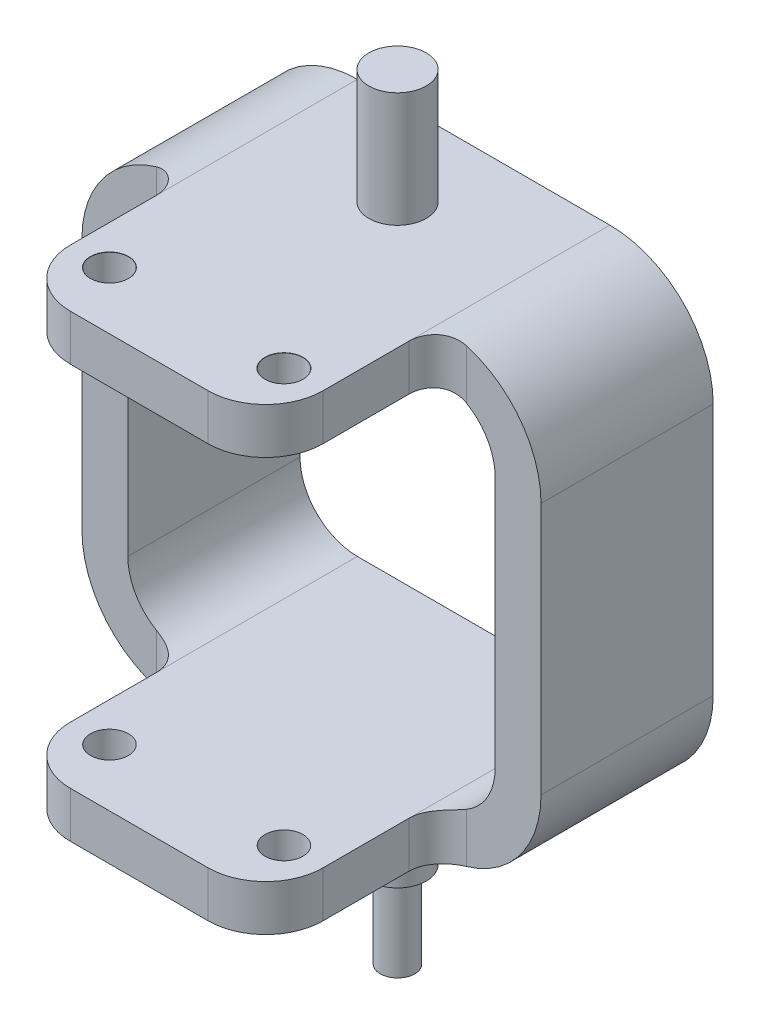
SolidWorks part; units mm, degrees
material "Plastique personnalisé"
ref_plane "Plan de face" through (0, 0, 0) normal (0, 0, 1) x (1, 0, 0)
ref_plane "Plan de dessus" through (0, 0, 0) normal (0, 1, 0) x (1, 0, 0)
ref_plane "Plan de droite" through (0, 0, 0) normal (1, 0, 0) x (0, 0, -1)
sketch "Esquisse1" plane through (0, 0, 0) normal (0, 0, 1) x (1, 0, 0)
  line L1 (40, -40) -> (-40, -40)
  line L2 (40, -40) -> (40, 40)
  line L3 (40, 40) -> (-40, 40)
  line L4 (-40, -40) -> (-40, 40)
  line L5 (40, -40) -> (-40, 40) construction
  line L6 (40, 40) -> (-40, -40) construction
  line L7 (-32, -32) -> (32, -32)
  line L8 (-32, -32) -> (-32, 32)
  line L9 (-32, 32) -> (32, 32)
  line L10 (32, -32) -> (32, 32)
  line L11 (-32, -32) -> (32, 32) construction
  line L12 (-32, 32) -> (32, -32) construction
  point P0 (0, 0)
  point P11 (0, 0)
  dimension "D1" = 8
  dimension "D3" = 80
extrude "Boss.-Extru.1" add sketch "Esquisse1" along normal mid plane 30
sketch "Esquisse2" plane through (0, 0, 0) normal (1, 0, 0) x (0, 0, -1)
  circle A0 centre (0, 0) radius 5
  dimension "D1" = 10
extrude "Enlèv. mat.-Extru.1" [suppressed] cut sketch "Esquisse2" against normal through all both and the other way through all
sketch "Esquisse3" plane through (0, -40, 0) normal (0, -1, 0) x (-1, 0, 0)
  circle A0 centre (0, 0) radius 5
  dimension "D1" = 10
extrude "Boss.-Extru.2" add sketch "Esquisse3" along normal blind 20
mirror "Symétrie1" about plane through (0, 0, 0) normal (0, 1, 0) of "Boss.-Extru.2"
fillet "Congé2" radius 18 4 edges at (40, -40, 0) (-40, -40, 0) (-40, 40, 0) (40, 40, 0)
fillet "Congé3" radius 10 4 edges at (-32, 32, 0) (-32, -32, 0) (32, -32, 0) (32, 32, 0)
sketch "Esquisse5" plane through (0, -60, 0) normal (0, -1, 0) x (1, 0, 0)
  circle A0 centre (0, 0) radius 3
  circle A1 centre (0, 0) radius 5 construction
  dimension "D1" = 6
extrude "Boss.-Extru.3" add sketch "Esquisse5" along normal blind 15
sketch "Esquisse6" plane through (0, -75, 0) normal (0, -1, 0) x (1, 0, 0)
  line L1 (3, -3) -> (-3, -3)
  line L2 (3, -3) -> (3, -1.8)
  line L3 (3, -1.8) -> (-3, -1.8)
  line L4 (-3, -3) -> (-3, -1.8)
  circle A0 centre (0, 0) radius 3 construction
  dimension "D1" = 1.2
extrude "Enlèv. mat.-Extru.2" cut sketch "Esquisse6" against normal up to surface (15 mm away) contours L1 L4 L3 L2 up to face at (0, -60, -3)
sketch "Esquisse7" plane through (0, 0, 15) normal (0, 0, 1) x (1, 0, 0)
  line L0 (22, 40) -> (-22, 40) construction
  line L1 (22, 32) -> (-22, 32)
  line L2 (22, 32) -> (22, 40)
  line L3 (22, 40) -> (-22, 40)
  line L4 (-22, 32) -> (-22, 40)
  line L6 (22, 32) -> (-22, 32) construction
  point P4 (0, 0)
  point P9 (0, 0)
extrude "Boss.-Extru.4" add sketch "Esquisse7" along normal blind 30
hole_wizard "Dégagement M61" positions "Esquisse10" profile "Esquisse9" hole size "M6" standard "Ansi Metric" end condition through all
sketch "Esquisse10" plane through (0, 40, 0) normal (0, -1, 0) x (0, 0, -1)
  line L0 (-35, 15.205) -> (-35, -15.205) construction
  line L3 (-35, 0) -> (-45, 0) construction
  line L6 (-45, 22) -> (-45, -22) construction
  point P0 (-35, 15.205)
  point P2 (-35, -15.205)
  point P20 (-45, 0)
  dimension "D1" = 30.41
  dimension "D2" = 10
sketch "Esquisse9" plane through (15.205, 40, 35) normal (1, 0, 0) x (0, 0, 1)
  line L0 (0, 0) -> (0, 115)
  line L1 (0, 115) -> (3.3, 115)
  line L2 (3.3, 115) -> (3.3, 0.025)
  line L3 (3.3, 0.025) -> (3.325, 0)
  line L5 (3.325, 0) -> (0, 0)
  line L6 (-3.3, 0.025) -> (-3.325, 0) construction
  line L11 (0, -6.35) -> (0, 107.95) construction
  dimension "Diamètre du perçage jusqu'au prochain" = 6.6
  dimension "Profondeur du perçage jusqu'au prochain" = 115
  dimension "Diamètre du fraisage entrant" = 6.65
  dimension "Angle du fraisage entrant" = 90
fillet "Congé1" radius 10 2 edges at (22, 36, 45) (-22, 36, 45)
mirror "Symétrie2" about plane through (0, 0, 0) normal (0, 1, 0) of "Boss.-Extru.4", "Dégagement M61", "Congé1"
fillet "Congé4" radius 5 4 edges at (-22, -36, 15) (-22, 36, 15) (22, -36, 15) (22, 36, 15)
